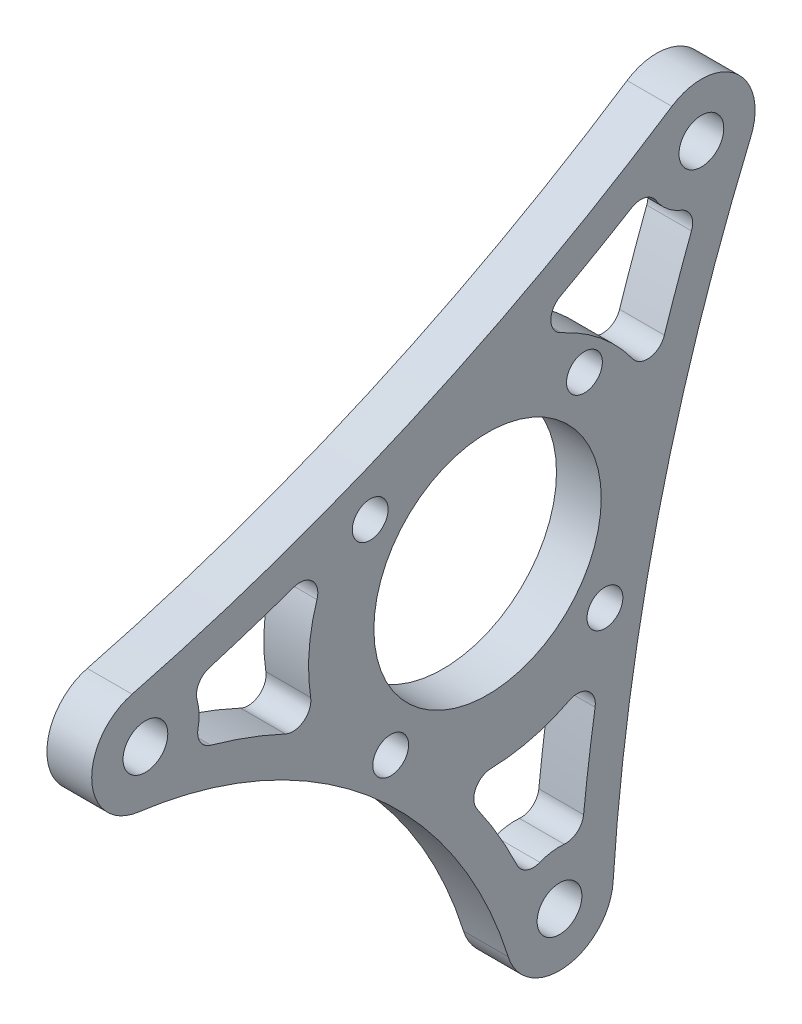
SolidWorks part; units mm, degrees
ref_plane "Front" through (0, 0, 0) normal (0, 0, 1) x (1, 0, 0)
ref_plane "Top" through (0, 0, 0) normal (0, 1, 0) x (1, 0, 0)
ref_plane "Right" through (0, 0, 0) normal (1, 0, 0) x (0, 0, -1)
sketch "Szkic1" plane through (0, 0, 0) normal (1, 0, 0) x (0, 0, -1)
  circle A0 centre (-38.2205, 1.4202) radius 2.5001
  circle A1 centre (8.0356, -37.3933) radius 2.5001
  circle A2 centre (0, 0) radius 12.7
  circle A3 centre (23.8844, 28.9378) radius 2.5001
  arc A4 (8.1143, 21.7992) -> (16.0855, 26.3774) centre (-89.4762, 200.9418) ccw
  arc A5 (12.0111, -19.8873) -> (10.7245, -29.6377) centre (213.5561, -51.4403) ccw
  arc A6 (12.0111, -19.8873) -> (9.1228, -17.7981) centre (10.0351, -19.578) ccw
  arc A7 (-32.3404, 0.227) -> (-30.9171, -2.0974) centre (-30.3803, -0.1708) ccw
  arc A8 (-19.0592, 6.062) -> (-21.6302, 8.5544) centre (-20.9651, 6.6682) ccw
  arc A9 (-31.0847, 5.4772) -> (-32.4393, 3.0257) centre (-30.5122, 3.5608) ccw
  arc A10 (0.4206, -19.9956) -> (-1.1756, -23.1423) centre (0.4627, -21.9951) ccw
  arc A11 (-22.5866, -5.1763) -> (-19.7648, -3.058) centre (-21.7413, -3.3638) ccw
  arc A12 (3.3032, -30.8116) -> (5.8394, -31.8097) centre (5.1073, -29.9485) ccw
  arc A13 (2.3094, -39.185) -> (-38.9907, -4.5301) centre (-45.4091, -54.1165) ccw
  arc A14 (18.8114, 25.734) -> (16.0855, 26.3774) centre (17.1204, 24.666) ccw
  arc A15 (8.5609, -31.4163) -> (10.7245, -29.6377) centre (8.736, -29.424) ccw
  arc A16 (8.1143, 21.7992) -> (8.2464, 18.2208) centre (9.0711, 20.0428) ccw
  arc A17 (22.7769, 20.8044) -> (21.651, 23.369) centre (20.9066, 21.5127) ccw
  arc A18 (16.2263, 11.6922) -> (19.749, 12.2371) centre (17.849, 12.8614) ccw
  arc A19 (-39.7134, 7.2316) -> (20.5827, 33.9477) centre (-89.4762, 200.9418) ccw
  arc A20 (-22.5866, -5.1763) -> (-30.9171, -2.0974) centre (-45.4091, -54.1165) ccw
  arc A21 (3.3032, -30.8116) -> (-1.1756, -23.1423) centre (-45.4091, -54.1165) ccw
  arc A22 (18.8114, 25.734) -> (21.651, 23.369) centre (23.8844, 28.9378) ccw
  arc A23 (8.5609, -31.4163) -> (5.8394, -31.8097) centre (8.0356, -37.3933) ccw
  arc A24 (-32.3404, 0.227) -> (-32.4393, 3.0257) centre (-38.2205, 1.4202) ccw
  arc A25 (29.4088, 26.5967) -> (20.5827, 33.9477) centre (23.8844, 28.9378) ccw
  arc A26 (22.7769, 20.8044) -> (19.749, 12.2371) centre (213.5561, -51.4403) ccw
  arc A27 (-31.0847, 5.4772) -> (-21.6302, 8.5544) centre (-89.4762, 200.9418) ccw
  arc A28 (0.4206, -19.9956) -> (9.1228, -17.7981) centre (0, 0) ccw
  arc A29 (2.3094, -39.185) -> (14.0216, -37.8024) centre (8.0356, -37.3933) ccw
  arc A30 (-39.7134, 7.2316) -> (-38.9907, -4.5301) centre (-38.2205, 1.4202) ccw
  arc A31 (29.4088, 26.5967) -> (14.0216, -37.8024) centre (213.5561, -51.4403) ccw
  arc A32 (16.2263, 11.6922) -> (8.2464, 18.2208) centre (0, 0) ccw
  arc A33 (-19.0592, 6.062) -> (-19.7648, -3.058) centre (0, 0) ccw
  circle A34 centre (13.111, -10.8214) radius 2
  circle A35 centre (10.8214, 13.111) radius 2
  circle A36 centre (-13.111, 10.8214) radius 2
  circle A37 centre (-10.8214, -13.111) radius 2
extrude "Dodanie-wyciągnięcie1" add sketch "Szkic1" along normal blind 5
